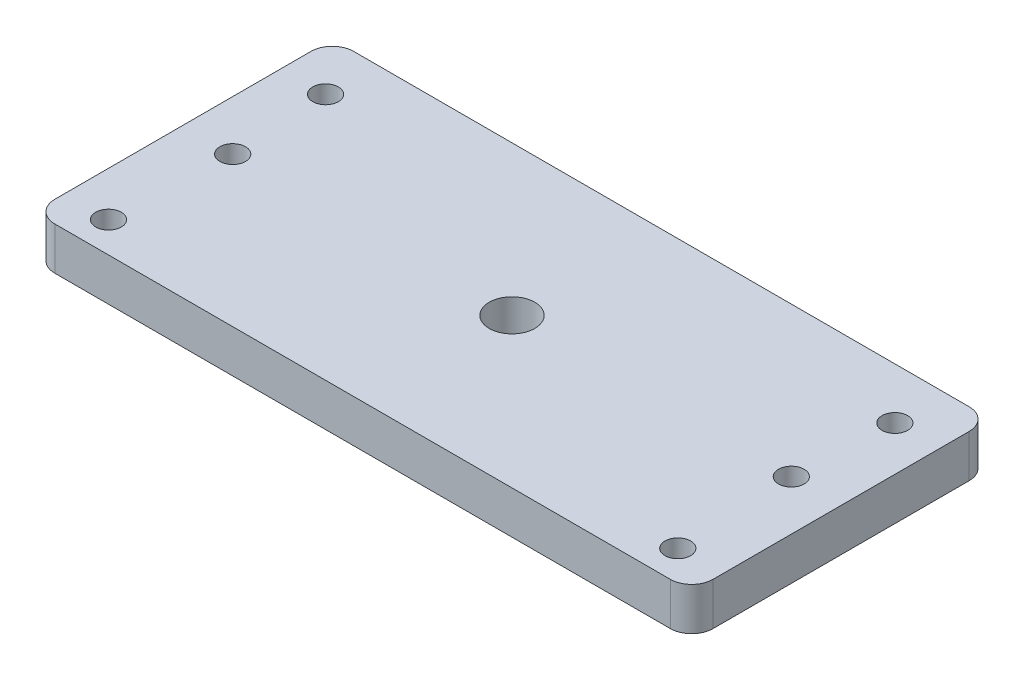
SolidWorks part; units mm, degrees
ref_plane "Płaszczyzna przednia" through (0, 0, 0) normal (0, 0, 1) x (1, 0, 0)
ref_plane "Płaszczyzna górna" through (0, 0, 0) normal (0, 1, 0) x (1, 0, 0)
ref_plane "Płaszczyzna prawa" through (0, 0, 0) normal (1, 0, 0) x (0, 0, -1)
sketch "Sketch2" plane through (0, 0, 0) normal (0, 1, 0) x (1, 0, 0)
  line L0 (-25.9967, 13.7153) -> (66.5033, 13.7153) construction
  line L1 (-25.9967, 34.7153) -> (66.5033, 34.7153)
  line L2 (-25.9967, 34.7153) -> (-25.9967, -7.2847)
  line L3 (-25.9967, -7.2847) -> (66.5033, -7.2847)
  line L4 (66.5033, 34.7153) -> (66.5033, -7.2847)
  line L5 (20.2533, 34.7153) -> (20.2533, -7.2847) construction
  circle A4 centre (20.2533, 13.7153) radius 3.2
  dimension "D6" = 6.4
extrude "Boss-Extrude1" add sketch "Sketch2" along normal blind 6
sketch "Sketch5" plane through (0, 0, 0) normal (0, -1, 0) x (-1, 0, 0)
  point P0 (-60.2533, 27.5153)
  point P3 (-60.2533, -2.9847)
  point P6 (19.7467, -2.9847)
  point P9 (19.7467, 27.5153)
hole_wizard "M3 Clearance Hole1" positions "Sketch5" profile "Sketch4" hole size "M3" standard "DIN"
sketch "Sketch4" plane through (60.2533, 0, -27.5153) normal (1, 0, 0) x (0, 0, -1)
  line L0 (0, 0) -> (0, 11.0815)
  line L1 (0, 11.0815) -> (1.8, 10)
  line L2 (1.8, 10) -> (1.8, 0)
  line L5 (1.8, 0) -> (0, 0)
  line L10 (0, 11.0815) -> (-1.8, 10) construction
  line L11 (0, -6.35) -> (0, 107.95) construction
  dimension "Hole Dia." = 3.6
  dimension "Hole Depth" = 10
  dimension "Drill Angle" = 118
sketch "Sketch7" plane through (0, 0, 0) normal (0, -1, 0) x (1, 0, 0)
  circle A0 centre (20.2533, -13.7153) radius 3.2 construction
  circle A1 centre (20.2533, -13.7153) radius 3.2
  circle A2 centre (20.2533, -13.7153) radius 7.2
  dimension "D1" = 4
extrude "Boss-Extrude2" add sketch "Sketch7" along normal blind 3
chamfer "Chamfer1" distance 3 angle 45 1 edges at (20.2533, 0, -6.5153)
fillet "Fillet1" radius 3 4 edges at (-25.9967, 3, -34.7153) (-25.9967, 3, 7.2847) (66.5033, 3, 7.2847) (66.5033, 3, -34.7153)
sketch "Sketch10" plane through (0, 0, 0) normal (0, -1, 0) x (-1, 0, 0)
  point P0 (-59.5033, 13.7153)
  point P2 (18.9967, 13.7153)
hole_wizard "CSK for M3 Hex Socket Countersunk Head Screw1" positions "Sketch10" profile "Sketch11" countersink size "M3" standard "DIN" end condition through all
sketch "Sketch11" plane through (59.5033, 0, -13.7153) normal (1, 0, 0) x (0, 0, -1)
  line L0 (0, 0) -> (0, 6)
  line L1 (0, 6) -> (1.8, 6)
  line L2 (1.8, 6) -> (1.8, 1.67)
  line L3 (1.8, 1.67) -> (3.47, 0)
  line L5 (3.47, 0) -> (0, 0)
  line L6 (-1.8, 1.67) -> (-3.47, 0) construction
  line L11 (0, -6.35) -> (0, 107.95) construction
  dimension "Thru Hole Dia." = 3.6
  dimension "Thru Hole Depth" = 6
  dimension "Near C'Sink Dia." = 6.94
  dimension "Near C'Sink Angle" = 90
